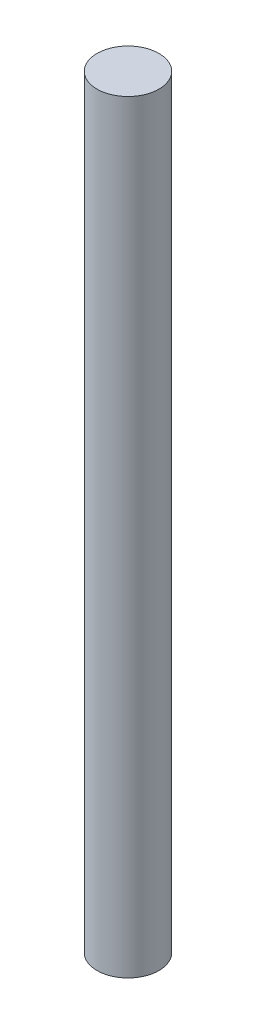
SolidWorks part; units mm, degrees
ref_plane "Front Plane" through (0, 0, 0) normal (0, 0, 1) x (1, 0, 0)
ref_plane "Top Plane" through (0, 0, 0) normal (0, 1, 0) x (1, 0, 0)
ref_plane "Right Plane" through (0, 0, 0) normal (1, 0, 0) x (0, 0, -1)
sketch "Sketch1" plane through (0, 0, 0) normal (0, 1, 0) x (1, 0, 0)
  circle A0 centre (0, 0) radius 1.5
  dimension "D1" = 3
extrude "Boss-Extrude1" add sketch "Sketch1" along normal blind 37
